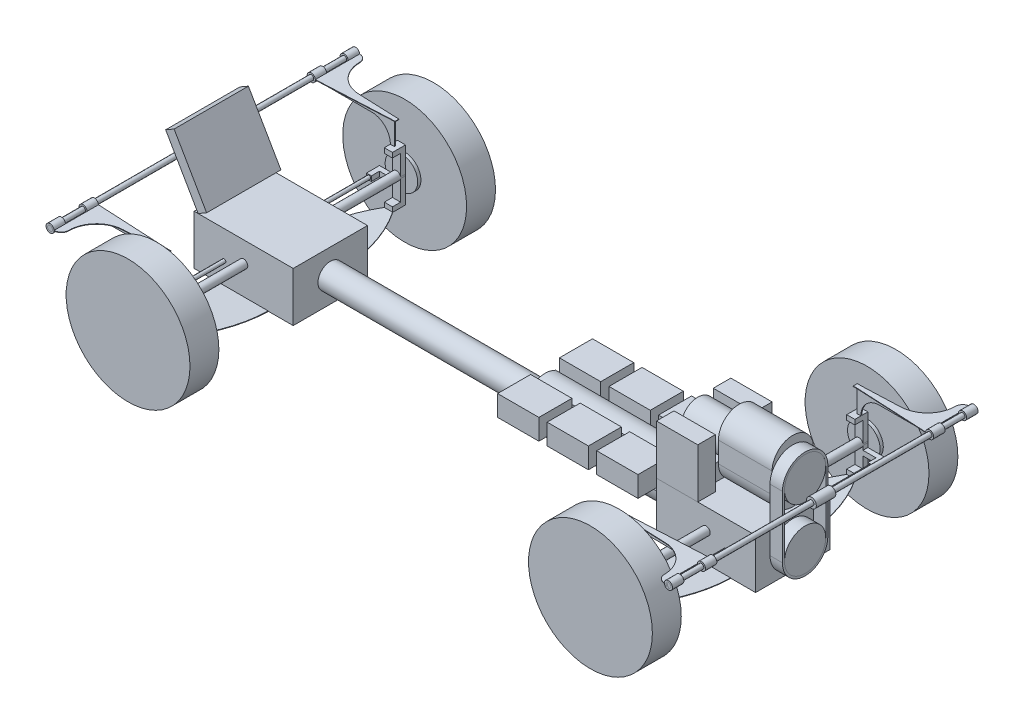
SolidWorks part; units mm, degrees
note: The reader was unsure of these and kept them because the rebuilt part matched: shared geometry of "Sketch5<3>", "Sketch6<3>", "Sketch12<3>", "Sketch16<3>", "Sketch16<4>", "Sketch17<3>", "Sketch17<4>", "Sketch17<5>", "Sketch98<4>".
ref_plane "Front Plane" through (0, 0, 0) normal (0, 0, 1) x (1, 0, 0)
ref_plane "Top Plane" through (0, 0, 0) normal (0, 1, 0) x (1, 0, 0)
ref_plane "Right Plane" through (0, 0, 0) normal (1, 0, 0) x (0, 0, -1)
sketch "Sketch1" plane through (0, 0, 0) normal (0, 1, 0) x (1, 0, 0)
  line L1 (-1422.4, -850.9) -> (1422.4, -850.9) construction
  line L2 (-1422.4, -850.9) -> (-1422.4, 850.9) construction
  line L3 (-1422.4, 850.9) -> (1422.4, 850.9) construction
  line L4 (1422.4, -850.9) -> (1422.4, 850.9) construction
  line L5 (-1422.4, -850.9) -> (1422.4, 850.9) construction
  line L6 (-1422.4, 850.9) -> (1422.4, -850.9) construction
  line L7 (-1727.2, -228.6) -> (-1117.6, -228.6)
  line L8 (-1727.2, -228.6) -> (-1727.2, 228.6)
  line L9 (-1727.2, 228.6) -> (-1117.6, 228.6)
  line L10 (-1117.6, -228.6) -> (-1117.6, 228.6)
  line L11 (-1727.2, -228.6) -> (-1117.6, 228.6) construction
  line L12 (-1727.2, 228.6) -> (-1117.6, -228.6) construction
  line L13 (1117.6, -228.6) -> (1727.2, -228.6)
  line L14 (1117.6, -228.6) -> (1117.6, 228.6)
  line L15 (1117.6, 228.6) -> (1727.2, 228.6)
  line L16 (1727.2, -228.6) -> (1727.2, 228.6)
  line L17 (1117.6, -228.6) -> (1727.2, 228.6) construction
  line L18 (1117.6, 228.6) -> (1727.2, -228.6) construction
  point P0 (0, 0)
  point P5 (-1422.4, 0)
  point P11 (1422.4, 0)
  dimension "D1" = 2844.8
  dimension "D2" = 1701.8
  dimension "D3" = 609.6
  dimension "D4" = 457.2
sketch "Sketch2" plane through (0, 0, 0) normal (0, 0, 1) x (1, 0, 0)
  line L0 (-1422.4, 0) -> (1422.4, 0) construction
  line L1 (-1422.4, 0) -> (1422.4, 0) construction
  line L2 (-1422.4, 0) -> (-1422.4, 381) construction
  line L3 (-1422.4, 381) -> (1422.4, 381) construction
  line L4 (1422.4, 381) -> (1422.4, 0) construction
  circle A0 centre (-1422.4, 381) radius 381
  circle A1 centre (1422.4, 381) radius 381
  dimension "D1" = 381
ref_plane "Plane1" through (0, 0, 850.9) normal (0, 0, 1) x (1, 0, 0)
ref_plane "Plane2" through (0, 0, -850.9) normal (0, 0, 1) x (1, 0, 0)
sketch "Sketch3" plane through (0, 0, 850.9) normal (0, 0, 1) x (1, 0, 0)
  circle A0 centre (1422.4, 381) radius 381 construction
  circle A1 centre (-1422.4, 381) radius 381 construction
  circle A2 centre (1422.4, 381) radius 381
  circle A3 centre (-1422.4, 381) radius 381
sketch "Sketch4" plane through (0, 0, -850.9) normal (0, 0, 1) x (1, 0, 0)
  circle A0 centre (1422.4, 381) radius 381 construction
  circle A1 centre (-1422.4, 381) radius 381 construction
  circle A2 centre (1422.4, 381) radius 381
  circle A3 centre (-1422.4, 381) radius 381
extrude "Boss-Extrude1" add sketch "Sketch4" along normal mid plane 177.8
extrude "Boss-Extrude2" add sketch "Sketch3" along normal mid plane 177.8 separate body contours A3 | A2
extrude "Boss-Extrude3" add sketch "Sketch1" along normal blind 304.8 from offset 203.2 separate body contours L13 L16 L15 L14 | L7 L10 L9 L8
sketch "Sketch5" plane through (1117.6, 0, 0) normal (-1, 0, 0) x (0, 0, 1)
  line L0 (0, 508) -> (0, 203.2) construction
  line L1 (0, 355.6) -> (0, 279.4) construction
  line L2 (0, 355.6) -> (-65.9911, 393.7) construction
  line L3 (0, 355.6) -> (65.9911, 393.7) construction
  line L4 (-228.6, 203.2) -> (228.6, 203.2)
  line L5 (228.6, 203.2) -> (228.6, 508)
  line L6 (228.6, 508) -> (-228.6, 508)
  line L7 (-228.6, 508) -> (-228.6, 203.2)
  line L8 (-228.6, 203.2) -> (228.6, 203.2) construction
  line L9 (228.6, 203.2) -> (228.6, 508) construction
  line L10 (228.6, 508) -> (-228.6, 508) construction
  line L11 (-228.6, 508) -> (-228.6, 203.2) construction
  line L12 (-228.6, 203.2) -> (228.6, 203.2)
  line L13 (228.6, 203.2) -> (228.6, 508)
  line L14 (228.6, 508) -> (-228.6, 508)
  line L15 (-228.6, 508) -> (-228.6, 203.2)
  line L16 (-228.6, 203.2) -> (228.6, 203.2) construction
  line L17 (228.6, 203.2) -> (228.6, 508) construction
  line L18 (228.6, 508) -> (-228.6, 508) construction
  line L19 (-228.6, 508) -> (-228.6, 203.2) construction
  line L20 (-65.9911, 393.7) -> (-65.9911, 478.7311)
  line L21 (65.9911, 393.7) -> (65.9911, 478.7311)
  line L22 (65.9911, 393.7) -> (139.6302, 351.1845)
  line L23 (0, 279.4) -> (73.6391, 236.8845)
  line L24 (0, 279.4) -> (-73.6391, 236.8845)
  line L25 (-65.9911, 393.7) -> (-139.6302, 351.1845)
  circle A0 centre (0, 355.6) radius 139.7 construction
  circle A1 centre (0, 355.6) radius 76.2
  arc A2 (65.9911, 478.7311) -> (-65.9911, 478.7311) centre (0, 355.6) ccw
  arc A3 (73.6391, 236.8845) -> (139.6302, 351.1845) centre (0, 355.6) ccw
  arc A4 (-139.6302, 351.1845) -> (-73.6391, 236.8845) centre (0, 355.6) ccw
  point P19 (0, 355.6)
  point P32 (0, 355.6)
  dimension "D3" = 279.4
  dimension "D4" = 152.4
  dimension "D5" = 76.2
  dimension "D1" = 0
  dimension "D2" = 0
extrude "Boss-Extrude4" add sketch "Sketch5" along normal blind 914.4 separate body contours L21 A2 L20 A1 | L23 A3 L22 A1 | L25 A4 L24 A1 | A1
extrude "Boss-Extrude5" add sketch "Sketch5<3>" along normal up to surface (2235.2 mm away) separate body contours A1 up to face at (-1117.6, 355.6, 0)
sketch "Sketch5<3>" plane through (1117.6, 0, 0) normal (-1, 0, 0) x (0, 0, 1) same geometry as "Sketch5"
sketch "Sketch6" plane through (1727.2, 0, 0) normal (1, 0, 0) x (0, 0, -1)
  line L0 (0, 736.6) -> (0, 355.6) construction
  line L1 (-127, 355.6) -> (-127, 736.6)
  line L2 (127, 736.6) -> (127, 355.6)
  line L3 (139.7, 736.6) -> (139.7, 355.6)
  line L4 (-139.7, 355.6) -> (-139.7, 736.6)
  circle A0 centre (0, 355.6) radius 127
  circle A1 centre (0, 736.6) radius 127
  arc A2 (-127, 736.6) -> (127, 736.6) centre (0, 736.6) cw
  arc A3 (127, 355.6) -> (-127, 355.6) centre (0, 355.6) cw
  arc A4 (-139.7, 736.6) -> (139.7, 736.6) centre (0, 736.6) cw
  arc A5 (139.7, 355.6) -> (-139.7, 355.6) centre (0, 355.6) cw
  dimension "D1" = 254
  dimension "D2" = 381
  dimension "D3" = 381
  dimension "D4" = 12.7
extrude "Boss-Extrude6" add sketch "Sketch6" along normal blind 76.2 separate body contours A1 | A0
sketch "Sketch8" plane through (1727.2, 0, 0) normal (-1, 0, 0) x (0, 0, 1)
  line L0 (0, 673.1) -> (0, 800.1) construction
  line L1 (-127, 673.1) -> (-127, 800.1)
  line L2 (127, 673.1) -> (127, 800.1)
  arc A0 (-127, 673.1) -> (127, 673.1) centre (0, 673.1) ccw
  circle A1 centre (0, 736.6) radius 127
  circle A2 centre (0, 736.6) radius 127 construction
  arc A3 (127, 800.1) -> (-127, 800.1) centre (0, 800.1) ccw
  point P5 (0, 736.6)
  dimension "D2" = 127
  dimension "D3" = 127
  dimension "D1" = 0
extrude "Boss-Extrude8" add sketch "Sketch8" along normal blind 330.2 separate body contours A3 L1 A0 L2
sketch "Sketch9" plane through (1397, 0, 0) normal (-1, 0, 0) x (0, 0, 1)
  line L0 (0, 800.1) -> (0, 673.1) construction
  line L2 (127, 673.1) -> (127, 800.1)
  line L3 (-127, 800.1) -> (-127, 673.1)
  line L4 (127, 673.1) -> (127, 800.1) construction
  line L5 (-127, 800.1) -> (-127, 673.1) construction
  line L6 (255.5028, 736.6) -> (255.5028, 737.5355) construction
  circle A0 centre (0, 736.6) radius 101.6
  arc A2 (127, 800.1) -> (-127, 800.1) centre (0, 800.1) ccw
  arc A3 (-127, 673.1) -> (127, 673.1) centre (0, 673.1) ccw
  arc A4 (127, 800.1) -> (-127, 800.1) centre (0, 800.1) ccw construction
  arc A5 (-127, 673.1) -> (127, 673.1) centre (0, 673.1) ccw construction
  dimension "D2" = 203.2
  dimension "D1" = 0
extrude "Boss-Extrude9" add sketch "Sketch9" along normal blind 254 separate body
extrude "Boss-Extrude10" add sketch "Sketch6<3>" along normal blind 76.2 separate body contours L4 A4 L3 A5 | L1 A2 L2 A3
sketch "Sketch6<3>" plane through (1727.2, 0, 0) normal (1, 0, 0) x (0, 0, -1) same geometry as "Sketch6"
ref_plane "Plane3" through (0, 406.4, 0) normal (0, 1, 0) x (1, 0, 0)
sketch "Sketch11" plane through (0, 406.4, 0) normal (0, 1, 0) x (1, 0, 0)
  line L0 (508, -88.6601) -> (508, -291.8601)
  line L1 (508, -88.6601) -> (762, -88.6601)
  line L2 (762, -88.6601) -> (762, -291.8601)
  line L3 (203.2, -88.6601) -> (457.2, -88.6601)
  line L4 (203.2, 0) -> (1117.6, 0) construction
  line L5 (203.2, 65.9911) -> (203.2, -65.9911) construction
  line L6 (1117.6, 228.6) -> (1117.6, -228.6) construction
  line L7 (203.2, -88.6601) -> (203.2, -291.8601)
  line L12 (203.2, -291.8601) -> (457.2, -291.8601)
  line L13 (457.2, -88.6601) -> (457.2, -291.8601)
  line L14 (508, -291.8601) -> (762, -291.8601)
  line L15 (812.8, -88.6601) -> (812.8, -291.8601)
  line L16 (812.8, -88.6601) -> (1066.8, -88.6601)
  line L17 (1066.8, -88.6601) -> (1066.8, -291.8601)
  line L18 (812.8, -291.8601) -> (1066.8, -291.8601)
  line L19 (812.8, 88.6601) -> (1066.8, 88.6601)
  line L20 (1066.8, 88.6601) -> (1066.8, 291.8601)
  line L21 (812.8, 291.8601) -> (1066.8, 291.8601)
  line L22 (812.8, 88.6601) -> (812.8, 291.8601)
  line L23 (508, 88.6601) -> (762, 88.6601)
  line L24 (762, 88.6601) -> (762, 291.8601)
  line L25 (508, 291.8601) -> (762, 291.8601)
  line L26 (508, 88.6601) -> (508, 291.8601)
  line L27 (203.2, 291.8601) -> (457.2, 291.8601)
  line L28 (457.2, 88.6601) -> (457.2, 291.8601)
  line L29 (203.2, 88.6601) -> (457.2, 88.6601)
  line L30 (203.2, 88.6601) -> (203.2, 291.8601)
  dimension "D1" = 203.2
  dimension "D2" = 254
  dimension "D3" = 3
extrude "Boss-Extrude11" add sketch "Sketch11" along normal blind 127 separate body contours L12 L13 L3 L7
sketch "Sketch12" plane through (0, 508, 0) normal (0, 1, 0) x (1, 0, 0)
  line L0 (1117.6, 228.6) -> (1371.6, 228.6)
  line L1 (1117.6, 228.6) -> (1727.2, 228.6) construction
  line L2 (1371.6, 228.6) -> (1371.6, 120.65)
  line L3 (1371.6, 120.65) -> (1117.6, 120.65)
  line L4 (1117.6, 120.65) -> (1117.6, 228.6)
  line L5 (1397, 0) -> (1117.6, 0) construction
  line L7 (1371.6, -120.65) -> (1117.6, -120.65)
  line L8 (1371.6, -228.6) -> (1371.6, -120.65)
  line L9 (1117.6, -228.6) -> (1371.6, -228.6)
  line L10 (1117.6, -120.65) -> (1117.6, -228.6)
  line L11 (1320.8, 120.65) -> (1320.8, -120.65)
  line L12 (1143, 120.65) -> (1143, -120.65)
  line L13 (1143, 120.65) -> (1320.8, 120.65)
  line L14 (1143, -120.65) -> (1320.8, -120.65)
  line M12 (1117.6, -228.6) -> (1727.2, -228.6)
  line M14 (1727.2, 228.6) -> (1117.6, 228.6)
  line M15 (1117.6, 228.6) -> (1117.6, -228.6)
  dimension "D1" = 254
  dimension "D2" = 107.95
  dimension "D3" = 177.8
  dimension "D4" = 50.8
extrude "Boss-Extrude12" add sketch "Sketch12" along normal blind 304.8 separate body contours L3 L2 M14 M15 | L8 L7 M12 M15
extrude "Boss-Extrude13" add sketch "Sketch12<3>" along normal blind 101.6 contours L11 L5 L12 L7 | L5 L11 L3 L12
sketch "Sketch12<3>" plane through (0, 508, 0) normal (0, 1, 0) x (1, 0, 0) same geometry as "Sketch12"
sketch "Sketch13" plane through (0, 0, -762) normal (0, 0, 1) x (1, 0, 0)
  circle A0 centre (-1422.4, 381) radius 25.4
  circle A1 centre (1422.4, 381) radius 25.4
  dimension "D1" = 50.8
extrude "Boss-Extrude15" add sketch "Sketch13" along normal up to surface (1524 mm away) up to face at (-1041.4, 381, 762)
sketch "Sketch15" plane through (0, 0, 228.6) normal (0, 0, 1) x (1, 0, 0)
  line L0 (-1902.2, 854.4102) -> (-1702.2, 508)
  line L1 (-1727.2, 508) -> (-1117.6, 508) construction
  line L2 (-1727.2, 508) -> (-1117.6, 508) construction
  line L3 (-1902.2, 854.4102) -> (-1850.2385, 884.4102)
  line L4 (-1850.2385, 884.4102) -> (-1650.2385, 538)
  line L5 (-1650.2385, 538) -> (-1702.2, 508)
  dimension "D1" = 60
  dimension "D2" = 400
  dimension "D3" = 60
  dimension "D4" = 25
extrude "Boss-Extrude16" add sketch "Sketch15" against normal up to surface (457.2 mm away) separate body up to face at (-1447.8, 381, -228.6)
sketch "Sketch16" plane through (0, 0, 762) normal (0, 0, -1) x (-1, 0, 0)
  line L0 (1397.4, 221) -> (1447.4, 541) construction
  line L1 (1447.4, 221) -> (1397.4, 541) construction
  line L2 (1397.4, 221) -> (1447.4, 221)
  line L3 (1447.4, 221) -> (1447.4, 541)
  line L4 (1447.4, 541) -> (1397.4, 541)
  line L5 (1397.4, 541) -> (1397.4, 221)
  line L6 (1397.4, 511) -> (1447.4, 511)
  line L7 (1447.4, 251) -> (1397.4, 251)
  line L8 (1447.4, 321) -> (1557.4, 321)
  line L9 (1557.4, 321) -> (1557.4, 351)
  line L10 (1557.4, 351) -> (1447.4, 351)
  line L11 (1527.4, 351) -> (1527.4, 321)
  circle A0 centre (1422.4, 381) radius 100
  circle A1 centre (1422.4, 381) radius 381
  circle A2 centre (1422.4, 381) radius 381 construction
  point P6 (1422.4, 381)
  point P9 (1422.4, 381)
  circle M11 centre (1422.4, 381) radius 25.4
  dimension "D10" = 200
  dimension "D2" = 320
  dimension "D3" = 50
  dimension "D4" = 30
  dimension "D5" = 30
  dimension "D6" = 30
  dimension "D7" = 30
  dimension "D8" = 100
  dimension "D9" = 110
  dimension "D1" = 0
extrude "Boss-Extrude17" add sketch "Sketch16" along normal blind 20 separate body contours A0
extrude "Boss-Extrude18" add sketch "Sketch16<3>" along normal blind 30 from surface at 20 contours L5 L6 L3 L4 | A0 L3 L6 L5 | L3 A0 L5 M11 | L5 A0 L3 M11 | A0 L5 L7 L3 | L3 L7 L5 L2 | L8 A0 L10 L3 | L10 L11 L8 L9 | A0 L8 L11 L10 starting at face at (-1522.4, 381, 742)
sketch "Sketch16<3>" plane through (0, 0, 762) normal (0, 0, -1) x (-1, 0, 0) same geometry as "Sketch16"
extrude "Boss-Extrude19" add sketch "Sketch16<4>" along normal blind 50 from surface at 50 contours L10 L11 L8 L9 | L5 L6 L3 L4 | L3 L7 L5 L2 starting at face at (-1422.4, 468.4725, 712)
sketch "Sketch16<4>" plane through (0, 0, 762) normal (0, 0, -1) x (-1, 0, 0) same geometry as "Sketch16"
ref_plane "Plane4" through (-1902.2, 0, 0) normal (-1, 0, 0) x (0, 0, 1)
sketch "Sketch17" plane through (-1902.2, 0, 0) normal (-1, 0, 0) x (0, 0, 1)
  line L0 (-939.8, 685) -> (939.8, 685)
  line L1 (-939.8, 762) -> (-939.8, 0) construction
  line L2 (939.8, 0) -> (939.8, 762) construction
  line L3 (-939.8, 0) -> (-762, 0) construction
  line L4 (-60, 685) -> (60, 685)
  line L5 (939.8, 685) -> (869.8, 685)
  line L6 (702, 541) -> (702, 685) construction
  line L7 (662, 541) -> (742, 541) construction
  line L8 (667, 685) -> (737, 685)
  point P10 (0, 685)
  point P11 (0, 685)
  point P20 (702, 685)
  dimension "D1" = 685
  dimension "D2" = 120
  dimension "D3" = 70
  dimension "D4" = 70
sweep "Sweep1" add path "Sketch17" circular profile diameter 30 parameters "D3"=30
sweep "Sweep2" add path "Sketch17<3>" circular profile diameter 60 parameters "D3"=60
sketch "Sketch17<3>" plane through (-1902.2, 0, 0) normal (-1, 0, 0) x (0, 0, 1) same geometry as "Sketch17"
sweep "Sweep3" add path "Sketch17<4>" circular profile diameter 50 parameters "D3"=50
sketch "Sketch17<4>" plane through (-1902.2, 0, 0) normal (-1, 0, 0) x (0, 0, 1) same geometry as "Sketch17"
sweep "Sweep4" add path "Sketch17<5>" circular profile diameter 50 parameters "D3"=50
sketch "Sketch17<5>" plane through (-1902.2, 0, 0) normal (-1, 0, 0) x (0, 0, 1) same geometry as "Sketch17"
ref_plane "Plane6" through (0, 685, 0) normal (0, 1, 0) x (1, 0, 0)
sketch "Sketch98" plane through (0, 685, 0) normal (0, 1, 0) x (1, 0, 0)
  line L0 (-1447.4, -662) -> (-1397.4, -742) construction
  line L1 (-1877.2, -667) -> (-1434.9, -689.5)
  line L2 (-1434.9, -714.5) -> (-1409.9, -714.5)
  line L3 (-1434.9, -714.5) -> (-1434.9, -689.5)
  line L4 (-1434.9, -689.5) -> (-1409.9, -689.5)
  line L5 (-1409.9, -714.5) -> (-1409.9, -689.5)
  line L6 (-1434.9, -714.5) -> (-1409.9, -689.5) construction
  line L7 (-1434.9, -689.5) -> (-1409.9, -714.5) construction
  line L8 (-1877.2, -667) -> (-1877.2, -939.8)
  line L9 (-1927.2, -939.8) -> (-1877.2, -939.8) construction
  line L10 (-1877.2, -895.4508) -> (-1832.8508, -895.4508) construction
  line L11 (-1667.7867, -723.7214) -> (-1434.9, -714.5)
  line L12 (-1422.4, -705) -> (-1422.4, -699)
  line L13 (-1422.4, -699) -> (-1877.2, -699)
  line L14 (-1422.4, -705) -> (-1877.2, -709)
  arc A0 (-1877.2, -939.8) -> (-1832.8508, -895.4508) centre (-1877.2, -895.4508) ccw
  arc A1 (-1832.8508, -895.4508) -> (-1667.7867, -723.7214) centre (-1660.9868, -895.4508) cw
  point P3 (-1422.4, -702)
  point P22 (-1422.4, -702)
  dimension "D3" = 6
  dimension "D1" = 25
  dimension "D2" = 25
  dimension "D4" = 10
extrude "Boss-Extrude20" add sketch "Sketch98" along normal mid plane 3
extrude "Boss-Extrude21" add sketch "Sketch98<4>" against normal up to surface (144 mm away) contours L14 L3 L13 L8 | L14 L12 L13 L3 up to face at (-1422.4, 541, 702)
sketch "Sketch98<4>" plane through (0, 685, 0) normal (0, 1, 0) x (1, 0, 0) same geometry as "Sketch98"
sketch "Sketch99" plane through (0, 0, 699) normal (0, 0, -1) x (-1, 0, 0)
  line L0 (1902.2, 655) -> (1561.4, 655)
  line L1 (1902.2, 541) -> (1902.2, 685) construction
  line L2 (1877.2, 541) -> (1422.4, 541) construction
  line L3 (1447.4, 541) -> (1447.4, 511) construction
  line L4 (1447.4, 541) -> (1877.2, 541)
  line L5 (1877.2, 541) -> (1902.2, 655)
  circle A0 centre (1902.2, 685) radius 30 construction
  arc A1 (1561.4, 655) -> (1447.4, 541) centre (1561.4, 541) ccw
extrude "Cut-Extrude1" cut sketch "Sketch99" against normal up to next
ref_plane "Plane7" through (0, 193.4849, -7.9465) normal (0, -0.9992, 0.041) x (-1, 0, 0)
sketch "Sketch100" plane through (0, 193.4849, -7.9465) normal (0, -0.9992, 0.041) x (-1, 0, 0)
  line L0 (1727.2, -236.746) -> (1117.6, -236.746) construction
  line L1 (1422.4, -670.5113) -> (1422.4, -236.746) construction
  line L2 (1447.4, -670.5113) -> (1397.4, -670.5113) construction
  line L3 (1271.0384, -236.746) -> (1573.7616, -236.746)
  line L4 (1397.4, -671.7424) -> (1447.4, -671.7424)
  arc A0 (1447.4, -671.7424) -> (1573.7616, -236.746) centre (803.8583, -248.9492) ccw
  arc A1 (1397.4, -671.7424) -> (1271.0384, -236.746) centre (2040.9417, -248.9492) cw
  dimension "D1" = 770
extrude "Boss-Extrude22" add sketch "Sketch100" along normal mid plane 3 separate body
sketch "Sketch101" plane through (0, 0, 662) normal (0, 0, -1) x (-1, 0, 0)
  line L0 (1527.4, 321) -> (1557.4, 351) construction
  line L1 (1527.4, 351) -> (1557.4, 351) construction
  line L2 (1557.4, 351) -> (1557.4, 321) construction
  circle A0 centre (1542.4, 336) radius 11
  dimension "D1" = 22
extrude "Boss-Extrude23" add sketch "Sketch101" along normal up to next (433.4 mm away) separate body contours A0
mirror "Mirror1" about plane through (0, 0, 0) normal (0, 0, 1) of bodies 129 132 133 136 137 138
mirror "Mirror2" about plane through (0, 0, 0) normal (1, 0, 0) of bodies 129 132 133 136 137 138 139 140 141 142 143 144
mirror "Mirror3" about plane through (0, 0, 0) normal (1, 0, 0) of bodies 131
